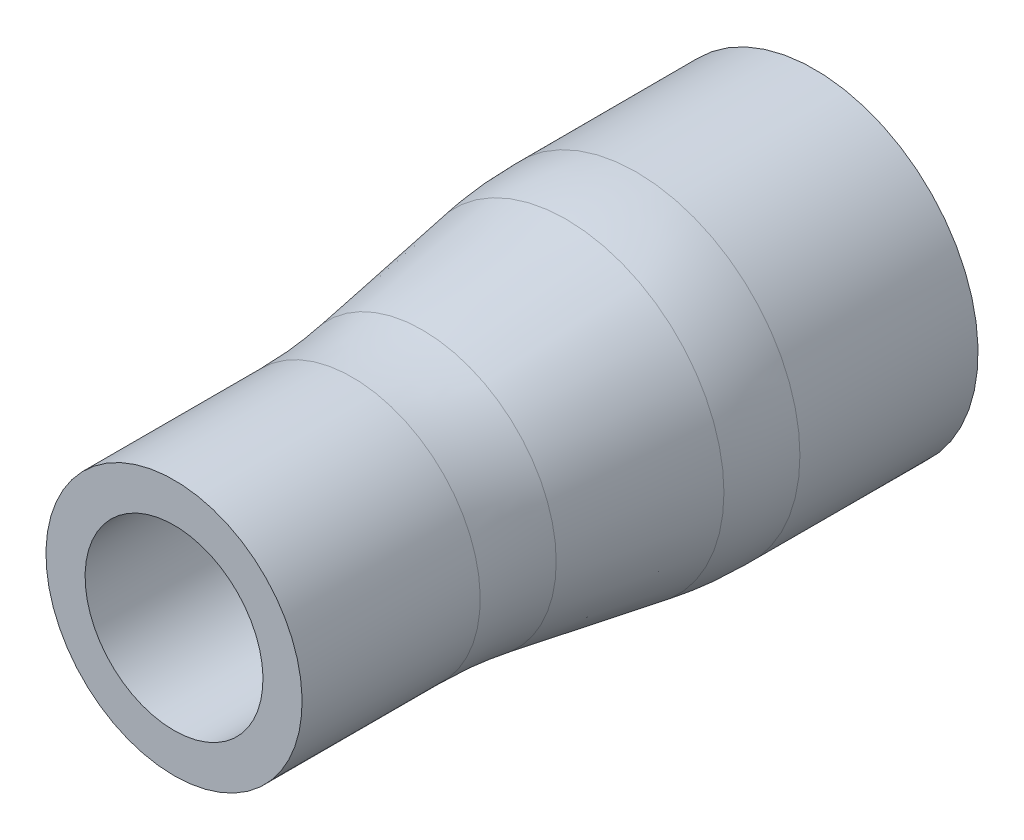
SolidWorks part; units mm, degrees
material "Silicon Rubber"
ref_plane "X-Y Datum" through (0, 0, 0) normal (0, 0, 1) x (1, 0, 0)
ref_plane "X-Z Datum" through (0, 0, 0) normal (0, 1, 0) x (1, 0, 0)
ref_plane "Y-Z Datum" through (0, 0, 0) normal (1, 0, 0) x (0, 0, -1)
sketch "Sketch1" plane through (0, 0, 0) normal (1, 0, 0) x (0, 0, -1)
  line L0 (-28.575, 11.43) -> (-9.525, 11.43)
  line L1 (-9.525, 11.43) -> (9.525, 14.605)
  line L2 (9.525, 14.605) -> (28.575, 14.605)
  line L4 (-9.525, 7.9375) -> (9.525, 9.525)
  line L7 (-28.575, 11.43) -> (-28.575, 7.9375)
  line L8 (-28.575, 7.9375) -> (-9.525, 7.9375)
  line L9 (28.575, 14.605) -> (28.575, 9.525)
  line L10 (28.575, 9.525) -> (9.525, 9.525)
  line L11 (-28.575, 0) -> (28.575, 0) construction
  point P7 (0, 13.0175)
  point P15 (0, 0)
  dimension "D1" = 19.05
  dimension "D2" = 19.05
  dimension "D3" = 9.525
  dimension "D4" = 7.9375
  dimension "D5" = 11.43
  dimension "D6" = 14.605
  dimension "D7" = 19.05
revolve "Revolve2" add sketch "Sketch1" angle 360 about L11
fillet "Fillet1" radius 38.1 4 edges at (0, -7.9375, 9.525) (0, -9.525, -9.525) (0, -14.605, -9.525) (0, -11.43, 9.525)
